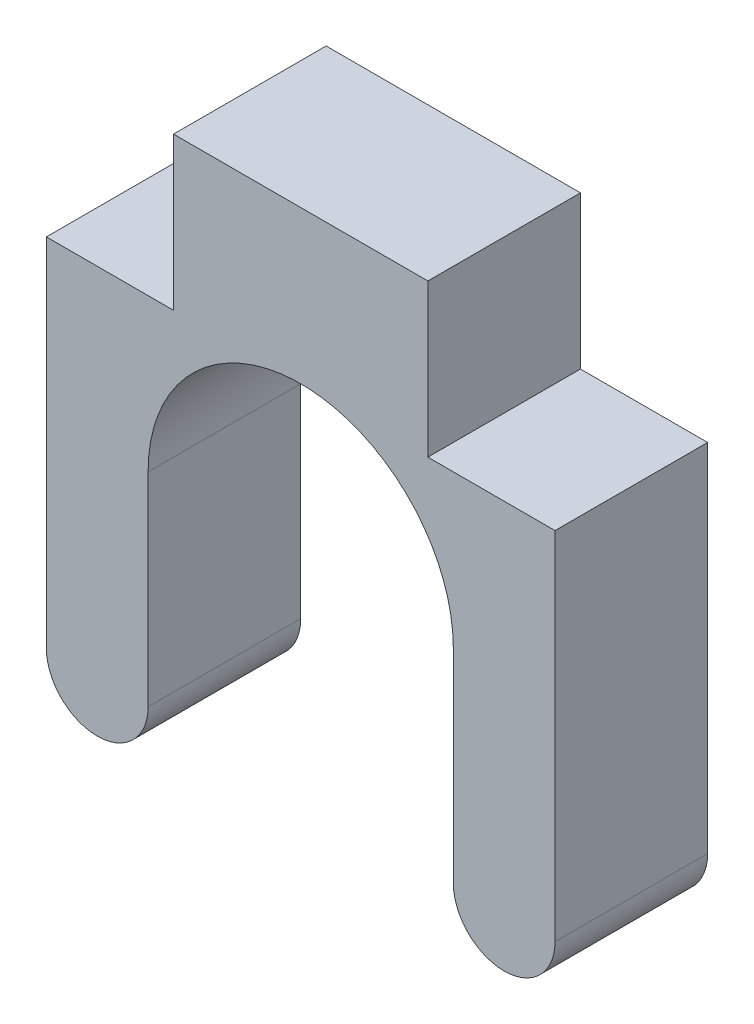
SolidWorks part; units mm, degrees
ref_plane "Front Plane" through (0, 0, 0) normal (0, 0, 1) x (1, 0, 0)
ref_plane "Top Plane" through (0, 0, 0) normal (0, 1, 0) x (1, 0, 0)
ref_plane "Right Plane" through (0, 0, 0) normal (1, 0, 0) x (0, 0, -1)
sketch "Sketch1" plane through (0, 0, 0) normal (0, 1, 0) x (1, 0, 0)
  line L0 (-450, 300) -> (-400, 300)
  line L1 (-400, 300) -> (-200, 250)
  line L2 (-200, 250) -> (200, 250) construction
  line L3 (200, 250) -> (600, 40) construction
  line L4 (600, 40) -> (1200, 40)
  line L5 (-450, -300) -> (-400, -300)
  line L6 (-400, -300) -> (-200, -250)
  line L7 (-200, -250) -> (200, -250) construction
  line L8 (200, -250) -> (600, -40) construction
  line L9 (600, -40) -> (1200, -40)
  line L10 (600, 40) -> (600, -40) construction
  line L11 (200, -250) -> (200, 250) construction
  line L12 (-200, 250) -> (-200, -250) construction
  line L13 (-400, -300) -> (-400, 300) construction
  line L14 (0, 0) -> (200, 0) construction
  line L15 (0, 250) -> (0, 0) construction
  line L16 (1200, 40) -> (1200, -40)
  line L17 (-450, 300) -> (-450, -300)
  line L18 (600, 0) -> (200, 0) construction
  line L19 (-450, 0) -> (-400, 0) construction
  line L20 (-400, 0) -> (-200, 0) construction
  line L21 (-200, 0) -> (0, 0) construction
  line L22 (-200, 250) -> (600, 40)
  line L23 (600, -40) -> (-200, -250)
  dimension "D1" = 600
  dimension "D2" = 200
  dimension "D3" = 50
  dimension "D4" = 400
  dimension "D5" = 500
  dimension "D6" = 80
  dimension "D7" = 600
  dimension "D8" = 400
extrude "Boss-Extrude1" add sketch "Sketch1" along normal blind 15
sketch "Sketch2" plane through (0, 0, 0) normal (0, 0, 1) x (1, 0, 0)
  line L0 (-450, 0) -> (-450, -40)
  line L1 (-450, -40) -> (-400, -40)
  line L2 (-400, -40) -> (-400, 0)
  line L3 (-400, 0) -> (-200, 0) construction
  line L4 (-400, 0) -> (-450, 0)
  line L5 (-440, -15) -> (-440, -40)
  line L6 (-410, -15) -> (-410, -40)
  line L7 (-425, 0) -> (-425, -15) construction
  circle A0 centre (-425, -15) radius 15
  dimension "D1" = 30
  dimension "D2" = 40
extrude "Boss-Extrude2" add sketch "Sketch2" along normal up to surface and the other way up to surface contours L4 L7 A0 L6 L1 L2 | L7 L4 L0 L1 L5 A0
sketch "Sketch4" plane through (0, 0, 0) normal (0, 1, 0) x (1, 0, 0)
  line L0 (-450, 230) -> (-400, 230)
  line L1 (-450, 300) -> (-450, -300) construction
  line L2 (-400, 230) -> (-150, 167.5)
  line L3 (-150, 167.5) -> (-150, -167.5)
  line L4 (-150, -167.5) -> (-400, -230)
  line L5 (-400, -230) -> (-450, -230)
  line L6 (-400, 230) -> (-400, -230) construction
  line L7 (-200, 250) -> (-200, -250) construction
  line L9 (-200, 0) -> (-150, 0) construction
  line L10 (-400, -230) -> (-400, -300) construction
  line L11 (-400, -300) -> (-200, -250) construction
  line L12 (-450, 230) -> (-450, -230)
  line L14 (-200, 250) -> (-400, 300) construction
  line L15 (-100, 155) -> (-100, -155)
  line L16 (-100, -155) -> (520, 0)
  line L17 (520, 0) -> (-100, 155)
  line L18 (520, 0) -> (-100, 0) construction
  dimension "D1" = 460
  dimension "D2" = 300
  dimension "D3" = 50
extrude "Cut-Extrude2" cut sketch "Sketch4" against normal through all both and the other way through all
sketch "Sketch5" plane through (0, 0, 0) normal (1, 0, 0) x (0, 0, -1)
  line L0 (-300, 0) -> (-230, 0) construction
  line L1 (-285, 0) -> (-245, 0)
  line L2 (-285, 0) -> (-285, -40)
  line L3 (-285, -40) -> (-245, -40)
  line L4 (-245, 0) -> (-245, -40)
  line L5 (-300, -40) -> (-230, -40) construction
  line L6 (230, 0) -> (300, 0) construction
  line L7 (245, 0) -> (285, 0)
  line L8 (245, 0) -> (245, -40)
  line L9 (245, -40) -> (285, -40)
  line L10 (285, 0) -> (285, -40)
  line L11 (230, -40) -> (300, -40) construction
  line L12 (-300, 0) -> (-300, -40) construction
  line L13 (230, -40) -> (230, 0) construction
  line L14 (300, 0) -> (300, -40) construction
  dimension "D1" = 15
  dimension "D2" = 15
  dimension "D3" = 15
  dimension "D4" = 15
extrude "Cut-Extrude3" cut sketch "Sketch5" against normal through all
sketch "Sketch7" plane through (1200, 0, 0) normal (1, 0, 0) x (0, 0, -1)
  line L1 (-40, 15) -> (-87.5, 50)
  line L2 (-87.5, 50) -> (-87.5, 88.7)
  line L3 (-87.5, 88.7) -> (87.5, 88.7)
  line L4 (87.5, 88.7) -> (87.5, 50)
  line L5 (87.5, 50) -> (40, 15)
  line L7 (-40, 15) -> (40, 15)
  line L8 (-20, 50) -> (-20, 88.7)
  line L9 (87.5, 50) -> (-87.5, 50) construction
  line L10 (0, 88.7) -> (0, 50) construction
  line L11 (-20, 88.7) -> (20, 88.7)
  line L12 (0, 50) -> (0, 0) construction
  line L13 (20, 88.7) -> (20, 50)
  line L14 (-73, 88.7) -> (-63, 88.7)
  line L15 (-73, 88.7) -> (-73, 63.2)
  line L16 (-73, 63.2) -> (-63, 63.2)
  line L17 (-63, 88.7) -> (-63, 63.2)
  line L18 (48.5, 88.7) -> (58.5, 88.7)
  line L19 (48.5, 88.7) -> (48.5, 63.2)
  line L20 (48.5, 63.2) -> (58.5, 63.2)
  line L21 (58.5, 88.7) -> (58.5, 63.2)
  circle A0 centre (0, 50) radius 20
  dimension "D3" = 40
  dimension "D1" = 175
  dimension "D2" = 50
  dimension "D4" = 25.5
  dimension "D5" = 10
  dimension "D6" = 63
  dimension "D7" = 48.5
  dimension "D8" = 38.7
extrude "Boss-Extrude4" add sketch "Sketch7" against normal blind 75
sketch "Sketch8" plane through (0, 0, 0) normal (0, 0, 1) x (1, 0, 0)
  line L0 (1125, 88.7) -> (1200, 88.7) construction
  line L1 (1140, 88.7) -> (1185, 88.7)
  line L2 (1140, 88.7) -> (1140, 15)
  line L3 (1140, 15) -> (1185, 15)
  line L4 (1185, 88.7) -> (1185, 15)
  line L5 (1125, 15) -> (1200, 15) construction
  line L6 (1125, 50) -> (1125, 88.7) construction
  line L7 (1200, 50) -> (1200, 88.7) construction
  line L8 (1155, 88.7) -> (1170, 88.7) construction
  line L9 (1155, 88.7) -> (1170, 88.7)
  line L10 (1155, 88.7) -> (1155, 15)
  line L11 (1155, 15) -> (1170, 15)
  line L12 (1170, 88.7) -> (1170, 15)
  line L15 (1162.5, 50) -> (1162.5, 88.7) construction
  line L16 (1125, 50) -> (1200, 50) construction
  line L17 (1155, 88.7) -> (1170, 88.7) construction
  dimension "D1" = 15
  dimension "D2" = 15
  dimension "D3" = 15
extrude "Cut-Extrude4" cut sketch "Sketch8" against normal through all both and the other way through all contours L10 L1 L2 L3 | L1 L12 L3 L4
fillet "Fillet1" radius 5 51 edges at (1192.5, 50, 87.5) (1162.5, 50, 87.5) (1132.5, 50, 87.5) (1192.5, 50, -87.5) (1162.5, 50, -87.5) (1132.5, 50, -87.5) (1192.5, 88.7, -87.5) (1162.5, 88.7, -87.5) (1132.5, 88.7, -87.5) (1132.5, 88.7, -58.5) (1162.5, 88.7, -58.5) (1192.5, 88.7, -58.5) (1192.5, 88.7, -48.5) (1162.5, 88.7, -48.5) (1132.5, 88.7, -48.5) (1192.5, 88.7, -20) (1162.5, 88.7, -20) (1132.5, 88.7, -20) (1192.5, 88.7, 63) (1162.5, 88.7, 63) (1132.5, 88.7, 63) (1132.5, 88.7, 87.5) (1162.5, 88.7, 87.5) (1192.5, 88.7, 87.5) (1192.5, 88.7, 73) (1162.5, 88.7, 73) (1132.5, 88.7, 73) (1192.5, 88.7, 20) (1162.5, 88.7, 20) (1132.5, 88.7, 20) (600, 7.5, 40) (600, 7.5, -40) (520, 7.5, 0) (-440, -40, -292.5) (-440, -40, -237.5) (-400, -40, -292.5) (-400, -40, -237.5) (-450, -40, 292.5) (-450, -40, 237.5) (-410, -40, -237.5) (-410, -40, -292.5) (-150, 7.5, 167.5) (-100, 7.5, 155) (-150, 7.5, -167.5) (-100, 7.5, -155) (-410, -40, 237.5) (-440, -40, 237.5) (-400, -40, 237.5) (-440, -40, 292.5) (-400, -40, 292.5) (-410, -40, 292.5)
sketch "Sketch9" plane through (0, 0, 0) normal (0, 1, 0) x (1, 0, 0)
  line L0 (1200, -40) -> (1200, 40) construction
  line L1 (-450, -300) -> (1200, -300)
  line L2 (-450, -300) -> (-450, 300)
  line L3 (-450, 300) -> (1200, 300)
  line L4 (1200, -300) -> (1200, 300)
  line L6 (-400, 285) -> (-450, 285)
  line L7 (-400, 285) -> (-400, 300)
  line L8 (-400, 300) -> (-450, 300)
  line L9 (-450, 285) -> (-450, 300)
extrude "Cut-Extrude5" cut sketch "Sketch9" against normal through all both and the other way through all contours L7 L6 L2 L1 L4 L3
sketch "Sketch10" plane through (0, 0, -285) normal (0, 0, 1) x (1, 0, 0)
  line L0 (-437.5, 0) -> (-412.5, 0) construction
  line L1 (-450, 15) -> (-437.5, 15)
  line L2 (-450, 15) -> (-450, 0)
  line L3 (-450, 0) -> (-437.5, 0)
  line L4 (-437.5, 15) -> (-437.5, 0)
  line L5 (-400, 15) -> (-412.5, 15)
  line L6 (-400, 15) -> (-400, 0)
  line L7 (-400, 0) -> (-412.5, 0)
  line L8 (-412.5, 15) -> (-412.5, 0)
  line L9 (-437.5, 0) -> (-412.5, 0)
  line L10 (-437.5, 15) -> (-412.5, 15)
  line L11 (-412.5, 0) -> (-437.5, 0)
  line M8 (-400, -35) -> (-400, 15)
  line M9 (-400, 15) -> (-450, 15)
  line M10 (-450, 15) -> (-450, -35)
  dimension "D1" = 25
  dimension "D2" = 15
extrude "Cut-Extrude6" cut sketch "Sketch10" against normal through all contours L4 L3 M9 M10 | L8 L7 M9 M8
